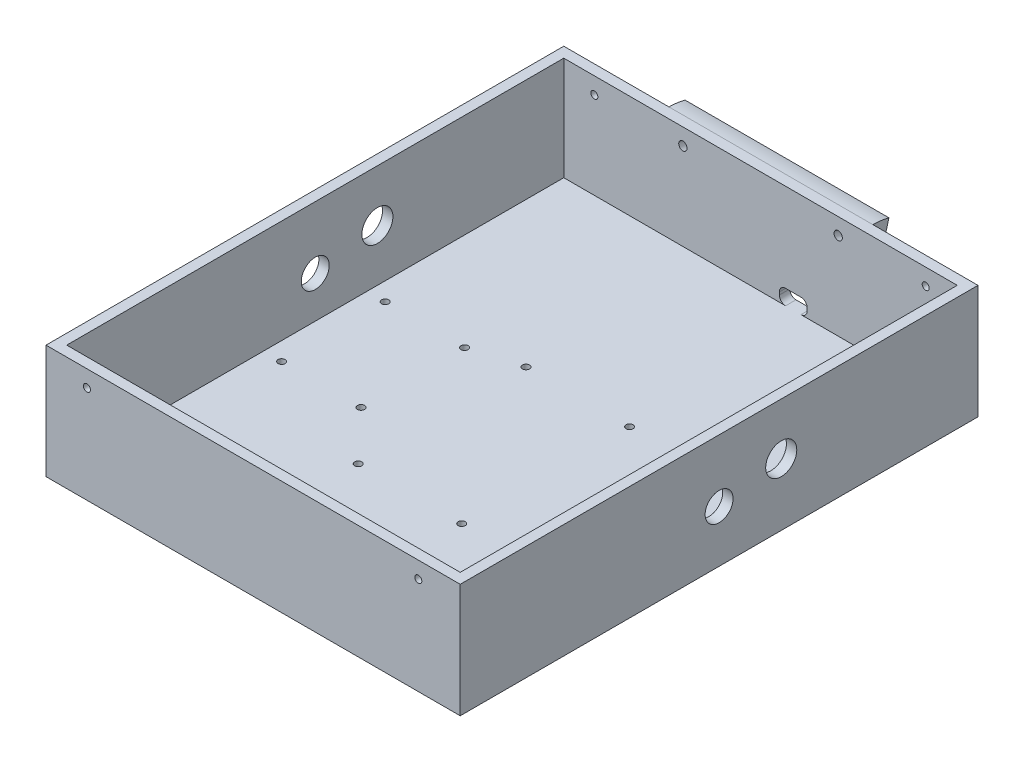
SolidWorks part; units mm, degrees
material "PLA 20%"
ref_plane "Front Plane" through (0, 0, 0) normal (0, 0, 1) x (1, 0, 0)
ref_plane "Top Plane" through (0, 0, 0) normal (0, 1, 0) x (1, 0, 0)
ref_plane "Right Plane" through (0, 0, 0) normal (1, 0, 0) x (0, 0, -1)
sketch "Sketch1" plane through (0, 0, 0) normal (0, 0, 1) x (1, 0, 0)
  line L0 (0, 50) -> (0, 0) construction
  line L1 (-95, 0) -> (95, 0)
  line L2 (-95, 0) -> (-95, 50)
  line L3 (-95, 50) -> (95, 50)
  line L4 (95, 0) -> (95, 50)
  dimension "D1" = 190
  dimension "D2" = 50
extrude "Boss-Extrude1" add sketch "Sketch1" along normal mid plane 240
shell "Shell1" thickness 5 removed face at (0, 50, 0) outward yes
sketch "Sketch3" plane through (100, 0, 0) normal (1, 0, 0) x (0, 0, -1)
  line L0 (-125, -5) -> (125, -5) construction
  line L1 (-15, -5) -> (15, -5)
  line L2 (-15, -5) -> (-15, 30)
  line L3 (-15, 30) -> (15, 30) construction
  line L4 (15, -5) -> (15, 30)
  line L5 (0, 30) -> (0, 20) construction
  line L6 (9.0631, 24.2262) -> (-0.618, 44.9873)
  line L7 (-15, 28.5056) -> (-9.0631, 15.7738)
  circle A0 centre (0, 20) radius 6.75
  arc A1 (-15, 30) -> (15, 30) centre (0, 30) cw
  circle A2 centre (0, 20) radius 10
  dimension "D2" = 13.5
  dimension "D5" = 20
  dimension "D1" = 25
  dimension "D3" = 30
  dimension "D4" = 10
  dimension "D6" = 25
extrude "Cut-Extrude2" cut sketch "Sketch3" against normal through all both and the other way through all contours A0 region at (100, 20, 0)
hole_wizard "M3 Clearance Hole1" positions "Sketch4" profile "Sketch5" hole size "M3" standard "ANSI Metric" end condition through all
sketch "Sketch4" plane through (0, 0, 125) normal (0, 0, 1) x (1, 0, 0)
  point P0 (-80.25, 42)
  point P1 (79.75, 42)
sketch "Sketch5" plane through (-80.25, 42, 125) normal (1, 0, 0) x (0, -1, 0)
  line L0 (0, 0) -> (0, 250)
  line L1 (0, 250) -> (1.7, 250)
  line L2 (1.7, 250) -> (1.7, 0)
  line L3 (1.7, 0) -> (0, 0)
  line L4 (0, -6.35) -> (0, 107.95) construction
  dimension "Thru Hole Dia." = 3.4
  dimension "Thru Hole Depth" = 250
sketch "Sketch8" plane through (0, 0, 0) normal (1, 0, 0) x (0, 0, -1)
  circle A0 centre (30, 25) radius 7.5
  dimension "D1" = 15
  dimension "D2" = 25
  dimension "D3" = 30
extrude "Cut-Extrude4" cut sketch "Sketch8" against normal through all both and the other way through all
sketch "Sketch10" plane through (0, 0, -125) normal (0, 0, -1) x (-1, 0, 0)
  line L0 (-100, -5) -> (-100, 50) construction
  line L5 (-22.5, 7.3) -> (-9.1, 7.3)
  line L6 (-22.5, 7.3) -> (-22.5, 0)
  line L7 (-22.5, 0) -> (-9.1, 0)
  line L8 (-9.1, 7.3) -> (-9.1, 0)
  line L9 (100, -5) -> (-100, -5) construction
  point P6 (-15.8, 0)
  dimension "D2" = 7.3
  dimension "D1" = 13.4
  dimension "D3" = 77.5
  dimension "D4" = 5
extrude "Cut-Extrude6" cut sketch "Sketch10" against normal up to surface (5 mm away) up to face at (-81.95, 42, -120)
fillet "Fillet1" radius 3 4 edges at (9.1, 0, -122.5) (22.5, 0, -122.5) (9.1, 7.3, -122.5) (22.5, 7.3, -122.5)
sketch "Sketch11" plane through (0, 0, -125) normal (0, 0, -1) x (-1, 0, 0)
  line L0 (-100, 50) -> (100, 50) construction
  line L1 (-49.2173, 20) -> (49.2173, 20)
  line L2 (-49.2173, 20) -> (-49.2173, 50)
  line L3 (-49.2173, 50) -> (49.2173, 50)
  line L4 (49.2173, 20) -> (49.2173, 50)
  line L5 (0, 0) -> (0, 50) construction
  dimension "D1" = 30
revolve "Revolve1" add sketch "Sketch11" angle 15 about L1
sketch "Sketch12" plane through (0, -29.9103, -111.6266) normal (0, -0.2588, -0.9659) x (-1, 0, 0)
  line L0 (0, 0) -> (0, 91.0316) construction
  line L1 (49.2173, 81.6709) -> (-49.2173, 81.6709) construction
  circle A0 centre (-37.5, 71.6709) radius 2
  dimension "D3" = 4
  dimension "D1" = 37.5
  dimension "D2" = 10
extrude "Cut-Extrude7" cut sketch "Sketch12" against normal up to surface (11.0713 mm away) up to face at (-81.95, 42, -120)
mirror "Mirror2" about plane through (0, 0, 0) normal (1, 0, 0) of "Cut-Extrude7"
hole_wizard "M3 Clearance Hole3" positions "Sketch16" profile "Sketch17" hole size "M3" standard "ANSI Metric"
sketch "Sketch16" plane through (0, 5, 0) normal (0, 1, 0) x (1, 0, 0)
  point P0 (-47.9032, 25)
  point P1 (-86.25, 25)
  point P2 (-47.9032, -25)
  point P3 (-86.25, -25)
  point P4 (25, -49.28)
  point P5 (47.9032, -25)
  point P6 (86.25, -25)
  point P7 (86.25, 25)
  point P8 (47.9032, 25)
  point P9 (25, 31.75)
  point P10 (-25, 31.75)
  point P11 (-25, -49.28)
sketch "Sketch17" plane through (-47.9032, 5, -25) normal (1, 0, 0) x (0, 0, 1)
  line L0 (0, 0) -> (0, 10)
  line L1 (0, 10) -> (1.7, 10)
  line L2 (1.7, 10) -> (1.7, 0)
  line L5 (1.7, 0) -> (0, 0)
  line L11 (0, -6.35) -> (0, 107.95) construction
  dimension "Thru Hole Dia." = 3.4
  dimension "Thru Hole Depth" = 10
